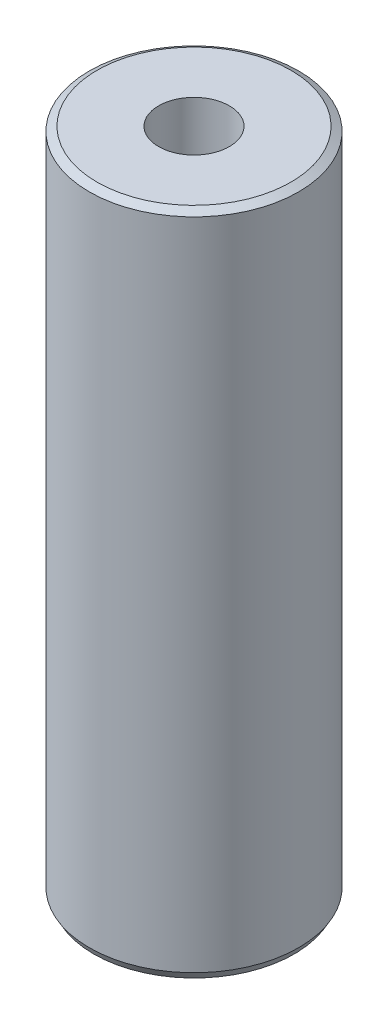
SolidWorks part; units mm, degrees
ref_plane "Front Plane" through (0, 0, 0) normal (0, 0, 1) x (1, 0, 0)
ref_plane "Top Plane" through (0, 0, 0) normal (0, 1, 0) x (1, 0, 0)
ref_plane "Right Plane" through (0, 0, 0) normal (1, 0, 0) x (0, 0, -1)
sketch "Sketch1" plane through (0, 0, 0) normal (0, 1, 0) x (1, 0, 0)
  circle A0 centre (0, 0) radius 25
  dimension "SHAFT_OD" = 50
extrude "Boss-Extrude1" add sketch "Sketch1" along normal blind 159.1816
sketch "Sketch2" plane through (0, 0, 0) normal (0, 1, 0) x (1, 0, 0)
  circle A0 centre (0, 0) radius 8.4459
  dimension "BORE_D" = 16.8919
extrude "Cut-Extrude1" cut sketch "Sketch2" along normal through all
chamfer "Chamfer1" distance 1.0729 angle 60 2 edges at (0, 159.1816, 25) (0, 0, 25) first distance on face at (0, 159.1816, 25) first distance on face at (0, 0, 8.4459)
